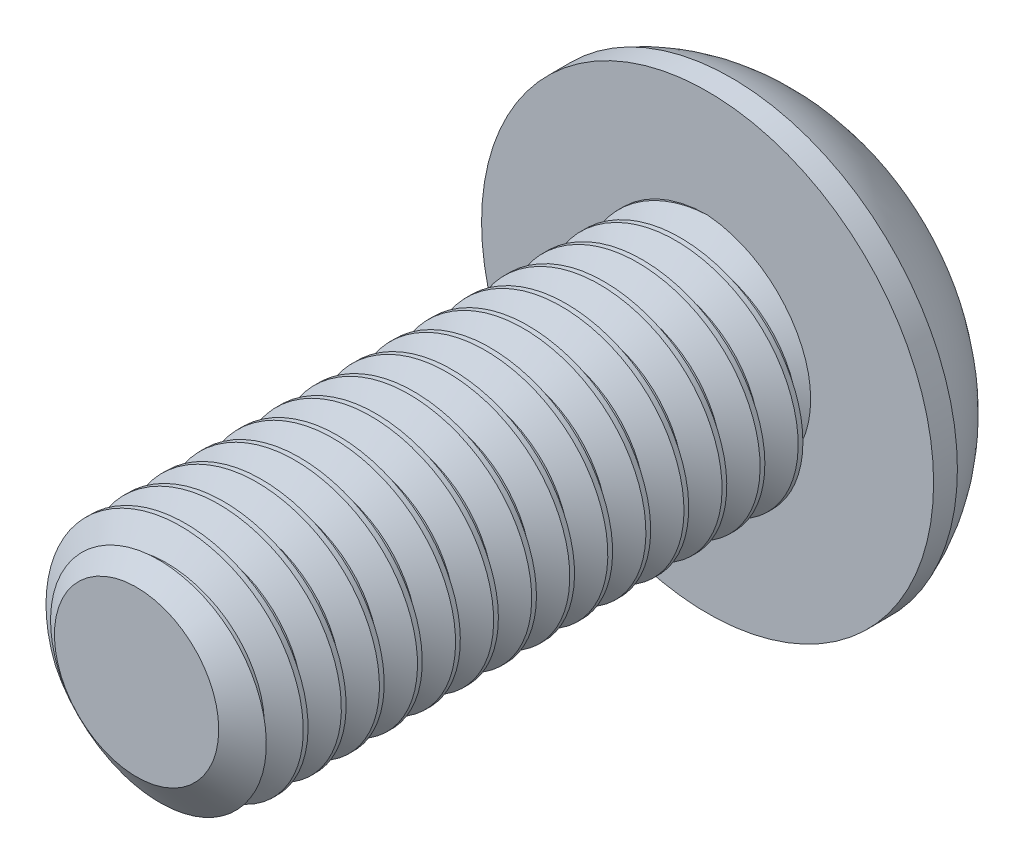
SolidWorks part; units mm, degrees
ref_plane "Front Plane" through (0, 0, 0) normal (0, 0, 1) x (1, 0, 0)
ref_plane "Top Plane" through (0, 0, 0) normal (0, 1, 0) x (1, 0, 0)
ref_plane "Right Plane" through (0, 0, 0) normal (1, 0, 0) x (0, 0, -1)
sketch "Sketch1" plane through (0, 0, 0) normal (0, 0, 1) x (1, 0, 0)
  circle A0 centre (0, 0) radius 2.5
  dimension "OD" = 5
extrude "Extrude1" add sketch "Sketch1" against normal blind 12
sketch "Sketch2" plane through (0, 0, 0) normal (0, 0, 1) x (1, 0, 0)
  circle A0 centre (0, 0) radius 2.5 construction
  circle A1 centre (0, 0) radius 2.5
curve "Helix/Spiral1" pitch 0.8 height 12.8 turns 16 parameters "pitch"=0.8
sketch "Sketch3" plane through (0, 0, 0) normal (1, 0, 0) x (0, 0, -1)
  line L0 (-0.7, 2.5) -> (-0.4, 1.9804)
  line L1 (-0.4, 1.9804) -> (-0.3, 1.9804)
  line L2 (-0.3, 1.9804) -> (0, 2.5)
  line L3 (-0.7, 2.5) -> (0, 2.5)
  line L4 (-0.35, 2.5) -> (-0.35, 1.9804) construction
  line L5 (-0.55, 2.2402) -> (-0.15, 2.2402) construction
  line L6 (0, 2.5) -> (0, -2.5) construction
  dimension "D1" = 0.1
  dimension "D2" = 0.4
  dimension "D3" = 60
sweep "Cut-Sweep1" cut profiles "Sketch3" path "Helix/Spiral1"
sketch "Sketch4" plane through (0, 0, 0) normal (1, 0, 0) x (0, 0, -1)
  line L0 (0.5417, 2.5) -> (0, 1.7264)
  line L1 (0, 1.7264) -> (0, 2.5)
  line L2 (0.5417, 2.5) -> (0, 2.5)
  line L3 (-0.7, 2.5) -> (0, 2.5) construction
  line L4 (0, 0) -> (7.0209, 0) construction
  dimension "D1" = 55
  dimension "D2" = 0.254
revolve "Cut-Revolve1" cut sketch "Sketch4" angle 360 about L4
sketch "Sketch5" plane through (0, 0, 0) normal (1, 0, 0) x (0, 0, -1)
  line L0 (12, -1.991) -> (12, 1.7838) construction
  line L1 (12, 2.627) -> (28.1202, 2.627)
  line L2 (12, 2.627) -> (12, 0)
  line L3 (12, 0) -> (28, 0)
  line L4 (28, 2.2968) -> (28, 0)
  line L5 (28.1202, 2.627) -> (28, 2.2968)
  line L6 (0, 0) -> (9.9695, 0) construction
  point P3 (28, 2.627)
  point P10 (28, 2.627)
  dimension "D1" = 0.3302
  dimension "Thread min" = 28
  dimension "D2" = 0.127
  dimension "D3" = 20
revolve "partially thread" [suppressed] add sketch "Sketch5" angle 360 about L6
sketch "Sketch6" plane through (0, 0, -12) normal (0, 0, -1) x (-1, 0, 0)
  circle A0 centre (0, 0) radius 4.75
  dimension "head dia" = 9.5
extrude "Extrude2" add sketch "Sketch6" along normal blind 2.75
sketch "Sketch10" plane through (0, 0, 0) normal (1, 0, 0) x (0, 0, -1)
  line L0 (14.75, -4.75) -> (14.75, 4.75) construction
  line L1 (0, 0) -> (15.9584, 0) construction
  line L2 (14.75, 4.75) -> (12, 4.75) construction
  line L3 (12, 4.75) -> (12, -4.75) construction
  line L4 (12.5, 4.75) -> (12.5, 5.25)
  line L5 (12.5, 5.25) -> (15.25, 5.25)
  line L6 (15.25, 5.25) -> (15.25, 1.5)
  line L7 (14.75, 1.5) -> (15.25, 1.5)
  arc A0 (14.75, 1.5) -> (12.5, 4.75) centre (11.2778, 1.5) ccw
  dimension "D1" = 3
  dimension "D2" = 0.5
  dimension "D3" = 0.5
revolve "Cut-Revolve2" cut sketch "Sketch10" angle 360 about L1
ref_plane "Plane1" through (0, 0, -14.75) normal (0, 0, 1) x (1, 0, 0)
sketch "Sketch7" plane through (0, 0, -14.75) normal (0, 0, -1) x (-1, 0, 0)
  line L1 (0, 1.7321) -> (-1.5, 0.866)
  line L2 (-1.5, 0.866) -> (-1.5, -0.866)
  line L3 (-1.5, -0.866) -> (0, -1.7321)
  line L4 (0, -1.7321) -> (1.5, -0.866)
  line L5 (1.5, -0.866) -> (1.5, 0.866)
  line L6 (1.5, 0.866) -> (0, 1.7321)
  circle A0 centre (0, 0) radius 1.5 construction
  dimension "hex dia" = 3
extrude "Cut-Extrude1" cut sketch "Sketch7" against normal blind 2.25
sketch "Sketch8" plane through (0, 0, -14.75) normal (0, 0, 1) x (1, 0, 0)
  circle A0 centre (0, 0) radius 1.7321
extrude "Cut-Extrude2" cut sketch "Sketch8" along normal through all draft 45
sketch "Sketch9" plane through (0, 0, 0) normal (1, 0, 0) x (0, 0, -1)
  line L0 (0, 2.5) -> (0, -2.5) construction
  line L1 (4.4, 2.5) -> (4.4, -2.5) construction
  dimension "D1" = 4.4
  dimension "D4" = 0.635
  dimension "D5" = 0.3302
equation "\"D3@Helix/Spiral1\" = \"screw length@Extrude1\"+\"pitch@Helix/Spiral1\""
equation "\"D1@Sketch3\" = \"pitch@Helix/Spiral1\"*.125"
equation "\"D2@Sketch3\" = \"pitch@Helix/Spiral1\"*.5"
equation "\"D1@Cut-Extrude1\" = \"hex dia@Sketch7\"*.75"
equation "\"D1@Sketch9\" = \"pitch@Helix/Spiral1\"*5.5"
equation "\"D1@Sketch10\" = \"hex dia@Sketch7\""
equation "\"D1@Plane1\" = \"head depth@Extrude2\""
